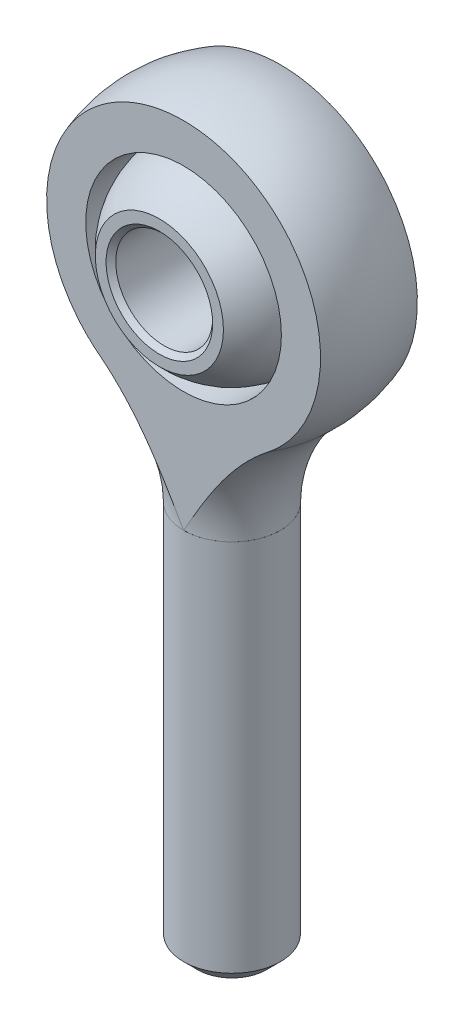
SolidWorks part; units mm, degrees
ref_plane "Front" through (0, 0, 0) normal (0, 0, 1) x (1, 0, 0)
ref_plane "Top" through (0, 0, 0) normal (0, 1, 0) x (1, 0, 0)
ref_plane "Right" through (0, 0, 0) normal (1, 0, 0) x (0, 0, -1)
sketch "Sketch1" plane through (0, 0, 0) normal (0, 0, 1) x (1, 0, 0)
  line L0 (0, 0) -> (0, -25.4)
  line L1 (0, -25.4) -> (3.175, -25.4)
  line L2 (3.175, -25.4) -> (3.175, 0)
  line L3 (3.175, 0) -> (0, 0)
  line L5 (0, 23.8125) -> (0, 0) construction
  line L6 (0, 23.8125) -> (9.525, 23.8125) construction
  line L7 (9.525, 23.8125) -> (9.525, 14.2875) construction
  line L8 (-3.175, -25.4) -> (-3.175, 0) construction
  line L9 (3.2732, -25.3433) -> (3.2732, -26.2501)
  line L10 (3.2732, -26.2501) -> (2.4879, -25.7967)
  line L11 (2.586, -25.8534) -> (2.586, -25.74)
  line L12 (2.4879, -25.7967) -> (3.2732, -25.3433)
  line L13 (3.2241, -25.3717) -> (3.2241, -26.2218)
  line L14 (3.2732, -25.7967) -> (3.175, -25.7967)
  line L15 (3.175, -25.4) -> (3.175, -26.1934)
  line L16 (2.4879, -25.7967) -> (2.586, -25.7967)
  arc A0 (6.3827, 7.2174) -> (0, 23.8125) centre (0, 14.2875) ccw construction
  circle A1 centre (0, 14.2875) radius 3.175 construction
  circle A2 centre (0, 14.2875) radius 6.35 construction
  circle A3 centre (0, 14.2875) radius 6.4135 construction
  arc A4 (3.175, 0) -> (6.3827, 7.2174) centre (12.8984, 0) cw construction
  point P24 (0, 20.6375)
  point P26 (3.175, -25.7967)
  point P28 (3.2241, -25.7967)
  dimension "A" = 6.35
  dimension "Ball Dia" = 12.7
  dimension "B" = 19.05
  dimension "D1" = 12.827
  dimension "D" = 39.6875
  dimension "E" = 25.4
  dimension "Thread Dia" = 6.35
  dimension "D2" = 60
  dimension "Pitch" = 0.9068
  dimension "D4" = 0.1133
sketch "Sketch2" plane through (0, 0, 0) normal (1, 0, 0) x (0, 0, -1)
  line L0 (3.175, 14.2875) -> (-3.175, 14.2875)
  line L1 (3.175, 15.0498) -> (0, 14.2875) construction
  line L2 (3.175, 13.5252) -> (0, 14.2875) construction
  line L6 (4.7625, 14.2875) -> (-4.7625, 14.2875)
  line L7 (0, 11.1125) -> (0, 17.4625)
  line L8 (0, 23.8125) -> (0, 0) construction
  line L9 (0, 17.4625) -> (0, 11.1125) construction
  circle A0 centre (0, 14.2875) radius 6.35
  circle A1 centre (0, 14.2875) radius 9.525
  point P4 (0, 14.2875)
  point P7 (0, 20.6375)
  point P9 (0, 7.9375)
  point P14 (0, 14.2875)
  point P18 (0, 14.2875)
  point P23 (9.525, 14.2875)
  point P25 (-9.525, 14.2875)
  dimension "OAWidth" = 6.35
  dimension "Swivel" = 27
  dimension "BallWidth" = 9.525
sketch "Sketch15" plane through (0, 0, 0) normal (0, 0, 1) x (1, 0, 0)
  line L0 (0, 23.8125) -> (0, 0) construction
  line L1 (9.525, 23.8125) -> (-9.525, 23.8125)
  line L2 (9.525, 23.8125) -> (9.525, 0)
  line L3 (9.525, 0) -> (-9.525, 0)
  line L4 (-9.525, 23.8125) -> (-9.525, 0)
  line L5 (3.175, 0) -> (0, 0) construction
  point P5 (0, 23.8125)
sketch "Sketch14" plane through (0, 0, 0) normal (0, 0, 1) x (1, 0, 0)
  line L1 (0, 0) -> (0, -25.4) construction
  line L2 (0, -25.4) -> (3.175, -25.4) construction
  line L3 (3.175, -25.4) -> (3.175, 0) construction
  line L5 (0, 0) -> (0, -25.4)
  line L6 (0, -25.4) -> (3.175, -25.4)
  line L7 (3.175, -25.4) -> (3.175, 0)
  line L8 (3.175, 0) -> (0, 0) construction
  line L9 (3.175, 0) -> (0, 0)
revolve "Revolve4" add sketch "Sketch14" angle 360 about L0
sketch "Sketch21" plane through (0, 0, 0) normal (0, 0, 1) x (1, 0, 0)
  line L0 (0, 23.8125) -> (0, 0) construction
  line L1 (3.175, 0) -> (0, 0) construction
  line L2 (0, 23.8125) -> (0, 0)
  line L3 (3.175, 0) -> (0, 0)
  arc A0 (6.3827, 7.2174) -> (3.175, 0) centre (12.8984, 0) ccw construction
  arc A1 (6.3827, 7.2174) -> (0, 23.8125) centre (0, 14.2875) ccw construction
  arc A2 (6.3827, 7.2174) -> (3.175, 0) centre (12.8984, 0) ccw
  arc A3 (6.3827, 7.2174) -> (0, 23.8125) centre (0, 14.2875) ccw
revolve "Revolve5" add sketch "Sketch21" angle 360 about L0
sketch "Sketch24" plane through (0, 0, 0) normal (1, 0, 0) x (0, 0, -1)
  line L0 (3.175, 14.2875) -> (3.175, 23.8125)
  line L1 (3.175, 23.8125) -> (9.525, 23.8125)
  line L2 (9.525, 0) -> (9.525, 23.8125)
  line L3 (3.175, 14.2875) -> (3.175, 0.635)
  line L4 (3.175, 0.635) -> (3.175, 0)
  line L5 (3.175, 0) -> (9.525, 0)
  line L6 (0, 23.8125) -> (0, 0) construction
  line L7 (0, 23.8125) -> (0, 0) construction
  line L8 (-3.175, 0) -> (-9.525, 0)
  line L9 (-3.175, 0.635) -> (-3.175, 0)
  line L10 (-3.175, 14.2875) -> (-3.175, 0.635)
  line L11 (-9.525, 0) -> (-9.525, 23.8125)
  line L12 (-3.175, 23.8125) -> (-9.525, 23.8125)
  line L13 (-3.175, 14.2875) -> (-3.175, 23.8125)
  dimension "D1" = 0.635
extrude "Cut-Extrude10" cut sketch "Sketch24" against normal through all both and the other way through all
sketch "Sketch17" plane through (0, 0, 0) normal (0, 0, 1) x (1, 0, 0)
  circle A2 centre (0, 14.2875) radius 6.4135 construction
  circle A3 centre (0, 14.2875) radius 6.4135
extrude "Cut-Extrude9" cut sketch "Sketch17" against normal through all both and the other way through all
sketch "Sketch7" plane through (0, 0, 0) normal (0, 0, 1) x (1, 0, 0)
  line L0 (0, 20.6375) -> (0, 7.9375)
  line L1 (0, 23.8125) -> (0, 0) construction
  line L2 (0, 0) -> (0, 7.9375) construction
  arc A0 (0, 7.9375) -> (0, 20.6375) centre (0, 14.2875) ccw
  circle A1 centre (0, 14.2875) radius 6.35 construction
revolve "Revolve3" add sketch "Sketch7" angle 360 about L2
sketch "Sketch10" plane through (0, 0, 0) normal (0, 0, 1) x (1, 0, 0)
  circle A0 centre (0, 14.2875) radius 3.175 construction
  circle A1 centre (0, 14.2875) radius 3.175
extrude "Cut-Extrude4" cut sketch "Sketch10" against normal through all and the other way through all
sketch "Sketch22" plane through (0, 0, 0) normal (0, 0, 1) x (1, 0, 0)
  line L0 (-9.525, 23.8125) -> (-9.525, 0) construction
  line L1 (9.525, 0) -> (-9.525, 0) construction
  line L2 (9.525, 23.8125) -> (9.525, 0) construction
  line L3 (9.525, 23.8125) -> (-9.525, 23.8125) construction
  line L4 (-9.525, 23.8125) -> (-9.525, 0)
  line L5 (9.525, 0) -> (-9.525, 0)
  line L6 (9.525, 23.8125) -> (9.525, 0)
  line L7 (9.525, 23.8125) -> (-9.525, 23.8125)
extrude "Cut-Extrude7" cut sketch "Sketch22" against normal through all from vertex starting at point (0, 14.2875, -4.7625)
sketch "Sketch23" plane through (0, 0, 0) normal (0, 0, 1) x (1, 0, 0)
  line L0 (-9.525, 23.8125) -> (-9.525, 0) construction
  line L1 (9.525, 0) -> (-9.525, 0) construction
  line L2 (9.525, 23.8125) -> (9.525, 0) construction
  line L3 (9.525, 23.8125) -> (-9.525, 23.8125) construction
  line L4 (-9.525, 23.8125) -> (-9.525, 0)
  line L5 (9.525, 0) -> (-9.525, 0)
  line L6 (9.525, 23.8125) -> (9.525, 0)
  line L7 (9.525, 23.8125) -> (-9.525, 23.8125)
extrude "Cut-Extrude8" cut sketch "Sketch23" along normal through all from vertex starting at point (0, 14.2875, 4.7625)
chamfer "Chamfer1" distance 0.9068 angle 45 1 edges at (-3.175, -25.4, 0)
chamfer "Chamfer2" distance 0.3175 angle 45 2 edges at (3.175, 14.2875, 4.7625) (3.175, 14.2875, -4.7625)
sketch "Sketch18" [suppressed] plane through (0, -25.4, 0) normal (0, -1, 0) x (1, 0, 0)
  circle A0 centre (0, 0) radius 3.175 construction
  circle A1 centre (0, 0) radius 3.175
curve "Helix/Spiral1" [suppressed] pitch 0.9068 height 26.3068 turns 29.0112
sketch "Sketch19" [suppressed] plane through (0, 0, 0) normal (0, 0, 1) x (1, 0, 0)
  line L0 (2.586, -25.8534) -> (2.586, -25.74) construction
  line L1 (2.4879, -25.7967) -> (3.2732, -25.3433) construction
  line L2 (3.2732, -26.2501) -> (2.4879, -25.7967) construction
  line L3 (3.2241, -25.3717) -> (3.2241, -26.2218) construction
  line L4 (2.586, -25.8534) -> (2.586, -25.74)
  line L5 (2.586, -25.74) -> (3.2241, -25.3717)
  line L6 (3.2241, -26.2218) -> (2.586, -25.8534)
  line L7 (3.2241, -25.3717) -> (3.2241, -26.2218)
sweep "Cut-Sweep1" [suppressed] cut profiles "Sketch19" path "Helix/Spiral1"
ref_plane "Plane1" [suppressed] through (0, 0, 0) normal (0, 1, 0) x (1, 0, 0)
sketch "Sketch20" [suppressed] plane through (0, 0, 0) normal (0, 1, 0) x (1, 0, 0)
  circle A0 centre (0, 0) radius 3.175
extrude "Boss-Extrude2" [suppressed] add sketch "Sketch20" against normal through all draft 60
combine bodies "Combine1" [suppressed] operation type add bodies to combine 130 133
sketch "Sketch25" plane through (0, 0, 0) normal (0, 0, 1) x (1, 0, 0)
  line L0 (0, -25.4) -> (0, 14.2875)
  line L1 (-2.2682, -25.4) -> (2.2682, -25.4) construction
  line L2 (0, -25.4) -> (0, -7.62)
  dimension "D1" = 17.78
move or copy body "Body-Move/Copy1" [suppressed] bodies to move or copy 122 132 133 parameters "D1"=0, "D2"=0, "D3"=0
move or copy body "Body-Move/Copy2" [suppressed] bodies to move or copy 136 137 138 parameters "D1"=0, "D2"=0, "D3"=0
move or copy body "Body-Move/Copy3" [suppressed] bodies to move or copy 139 140 141 parameters "D1"=0, "D2"=0, "D3"=0
move or copy body "Body-Move/Copy4" [suppressed] bodies to move or copy 142 143 144 parameters "D1"=0, "D2"=0, "D3"=0
equation "\"D1@Sketch1\"=\"Ball Dia@Sketch1\"*1.01"
equation "\"D1\"= \"A@Sketch1\" / 20"
equation "\"D3\"= \"E@Sketch1\" + .2"
equation "\"D4@Sketch1\"=\"Pitch@Sketch1\"/8"
equation "\"D1@Chamfer1\"=\"Pitch@Sketch1\""
equation "\"D4@Helix/Spiral1\"=\"Pitch@Sketch1\""
equation "\"D3@Helix/Spiral1\"=\"E@Sketch1\"+\"Pitch@Sketch1\""
equation "\"D1@Chamfer2\"=\"A@Sketch1\"/20"
equation "\"D1@Sketch24\"=(\"OAWidth@Sketch2\"/2)/5"
